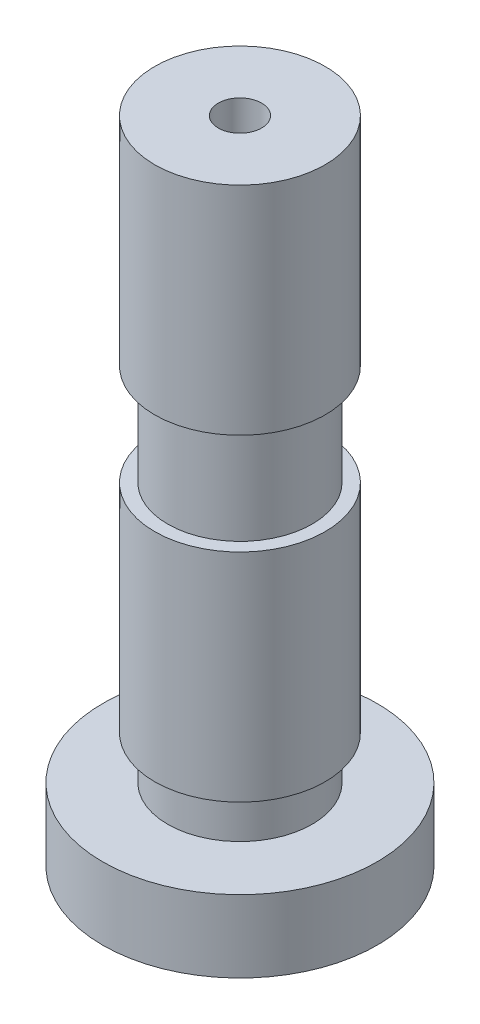
SolidWorks part; units mm, degrees
ref_plane "Спереди" through (0, 0, 0) normal (0, 0, 1) x (1, 0, 0)
ref_plane "Сверху" through (0, 0, 0) normal (0, 1, 0) x (1, 0, 0)
ref_plane "Справа" through (0, 0, 0) normal (1, 0, 0) x (0, 0, -1)
sketch "Эскиз1" plane through (0, 0, 0) normal (0, 0, 1) x (1, 0, 0)
  line L0 (0, 14.6468) -> (0, -10.5782) construction
  line L1 (0, 0) -> (9.5, 0)
  line L2 (9.5, 0) -> (9.5, 5)
  line L3 (9.5, 5) -> (5, 5)
  line L4 (5, 5) -> (5, 8)
  line L5 (5, 8) -> (5.9, 8)
  line L6 (5.9, 8) -> (5.9, 23)
  line L7 (5.9, 23) -> (5, 23)
  line L9 (5.9, 45) -> (0, 45)
  line L10 (0, 45) -> (0, 0)
  line L11 (5, 23) -> (5, 30)
  line L12 (5, 30) -> (5.9, 30)
  line L13 (5.9, 30) -> (5.9, 45)
  point P16 (0, 0)
  point P17 (0, 0)
  point P18 (4.0328, 30.9017)
  dimension "D1" = 19
  dimension "D2" = 5
  dimension "D3" = 3
  dimension "D4" = 45
  dimension "D5" = 15
  dimension "D6" = 7
  dimension "D7" = 11.8
  dimension "D8" = 10
revolve "Повернуть1" add sketch "Эскиз1" angle 360 about L0
sketch "Эскиз2" plane through (0, 45, 0) normal (0, 1, 0) x (1, 0, 0)
  circle A0 centre (0, 0) radius 1.5
  dimension "D1" = 3
extrude "Вырез-Вытянуть1" cut sketch "Эскиз2" against normal blind 3
sketch "Эскиз3" plane through (0, 0, 0) normal (0, -1, 0) x (-1, 0, 0)
  circle A0 centre (0, 0) radius 1.5
  dimension "D1" = 3
extrude "Вырез-Вытянуть2" cut sketch "Эскиз3" against normal blind 3
